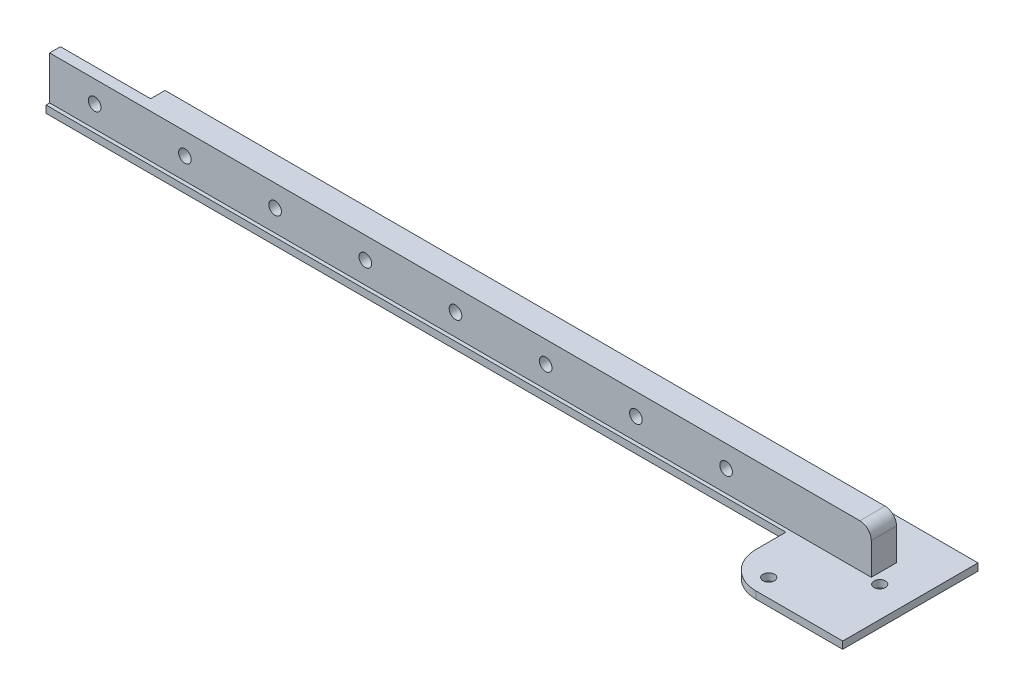
SolidWorks part; units mm, degrees
ref_plane "Front Plane" through (0, 0, 0) normal (0, 0, 1) x (1, 0, 0)
ref_plane "Top Plane" through (0, 0, 0) normal (0, 1, 0) x (1, 0, 0)
ref_plane "Right Plane" through (0, 0, 0) normal (1, 0, 0) x (0, 0, -1)
sketch "TopSketch1" plane through (0, 0, 0) normal (0, 1, 0) x (1, 0, 0)
  line L0 (0, 0) -> (34, 0)
  line L1 (34, 0) -> (34, 37.5)
  line L2 (34, 37.5) -> (0, 37.5)
  line L3 (0, 37.5) -> (0, 26.25)
  line L7 (0, 18.25) -> (0, 0)
  line L8 (0, 18.25) -> (-205.08, 18.25)
  line L9 (-205.08, 18.25) -> (-205.08, 26.25)
  line L10 (-205.08, 26.25) -> (0, 26.25)
  circle A0 centre (8.5, 32.5) radius 1.59
  circle A1 centre (8.5, 5) radius 1.59
  circle A3 centre (25.5, 18.75) radius 1.59
  dimension "D6" = 3.18
  dimension "D1" = 37.5
  dimension "D2" = 34
  dimension "D5" = 8.5
  dimension "D7" = 5
  dimension "D8" = 5
  dimension "D3" = 205.08
  dimension "D4" = 8
  dimension "D9" = 8.5
  dimension "D10" = 18.75
  dimension "D11" = 11.25
  dimension "D12" = 18.25
  dimension "D13" = 239.08
extrude "TopBoss-Extrude1" add sketch "TopSketch1" along normal blind 2
fillet "Fillet1" radius 10 2 edges at (0, 1, 0) (0, 1, -37.5)
sketch "LinearRailHEightSketch2" plane through (0, 2, 0) normal (0, 1, 0) x (1, 0, 0)
  line L0 (0, 26.25) -> (-205.08, 26.25) construction
  line L1 (-205.08, 26.25) -> (22.6667, 26.25)
  line L2 (-205.08, 26.25) -> (-205.08, 19.25)
  line L3 (-205.08, 19.25) -> (22.6667, 19.25)
  line L4 (22.6667, 26.25) -> (22.6667, 19.25)
  line L5 (-205.08, 26.25) -> (-205.08, 18.25) construction
  line L7 (-205.08, 18.25) -> (0, 18.25) construction
  line L8 (34, 0) -> (34, 37.5) construction
  dimension "D1" = 1
  dimension "D2" = 11.3333
extrude "LinearRailHeightBoss-Extrude2" add sketch "LinearRailHEightSketch2" along normal blind 12
sketch "LinearRailHolesSketch3" plane through (0, 0, -19.25) normal (0, 0, 1) x (1, 0, 0)
  line L0 (-205.08, 2) -> (22.6667, 2) construction
  line L1 (-205.08, 14) -> (-205.08, 2) construction
  circle A0 centre (-192.58, 8) radius 1.75
  circle A1 centre (-167.58, 8) radius 1.75
  circle A2 centre (-142.58, 8) radius 1.75
  circle A3 centre (-117.58, 8) radius 1.75
  circle A4 centre (-92.58, 8) radius 1.75
  circle A5 centre (-67.58, 8) radius 1.75
  circle A6 centre (-42.58, 8) radius 1.75
  circle A7 centre (-17.58, 8) radius 1.75
  dimension "D4" = 8
  dimension "D1" = 3.5
  dimension "D2" = 6
  dimension "D3" = 12.5
extrude "LinearRailHolesCut-Extrude1" cut sketch "LinearRailHolesSketch3" against normal through all
sketch "ConnectingPlateSketch2" plane through (0, 0, -26.25) normal (0, 0, -1) x (-1, 0, 0)
  line L0 (-22.6667, 14) -> (205.08, 14) construction
  line L1 (180.08, 14) -> (205.08, 14)
  line L2 (180.08, 14) -> (180.08, 0)
  line L3 (180.08, 0) -> (205.08, 0)
  line L4 (205.08, 14) -> (205.08, 0)
  dimension "D1" = 25
extrude "ConnectingPlateCut-Extrude1" cut sketch "ConnectingPlateSketch2" against normal blind 4
fillet "Fillet2" radius 3.175 1 edges at (22.6667, 14, -22.75)
sketch "NutHoleSketch1" plane through (0, 0, -26.25) normal (0, 0, -1) x (-1, 0, 0)
  line L1 (19.13, 5.3153) -> (20.68, 8)
  line L2 (20.68, 8) -> (19.13, 10.6847)
  line L3 (19.13, 10.6847) -> (16.03, 10.6847)
  line L4 (16.03, 10.6847) -> (14.48, 8)
  line L5 (14.48, 8) -> (16.03, 5.3153)
  line L6 (16.03, 5.3153) -> (19.13, 5.3153)
  line L7 (44.13, 5.3153) -> (45.68, 8)
  line L8 (45.68, 8) -> (44.13, 10.6847)
  line L9 (44.13, 10.6847) -> (41.03, 10.6847)
  line L10 (41.03, 10.6847) -> (39.48, 8)
  line L11 (39.48, 8) -> (41.03, 5.3153)
  line L12 (41.03, 5.3153) -> (44.13, 5.3153)
  line L13 (69.13, 5.3153) -> (70.68, 8)
  line L14 (70.68, 8) -> (69.13, 10.6847)
  line L15 (69.13, 10.6847) -> (66.03, 10.6847)
  line L16 (66.03, 10.6847) -> (64.48, 8)
  line L17 (64.48, 8) -> (66.03, 5.3153)
  line L18 (66.03, 5.3153) -> (69.13, 5.3153)
  line L19 (94.13, 5.3153) -> (95.68, 8)
  line L20 (95.68, 8) -> (94.13, 10.6847)
  line L21 (94.13, 10.6847) -> (91.03, 10.6847)
  line L22 (91.03, 10.6847) -> (89.48, 8)
  line L23 (89.48, 8) -> (91.03, 5.3153)
  line L24 (91.03, 5.3153) -> (94.13, 5.3153)
  line L25 (119.13, 5.3153) -> (120.68, 8)
  line L26 (120.68, 8) -> (119.13, 10.6847)
  line L27 (119.13, 10.6847) -> (116.03, 10.6847)
  line L28 (116.03, 10.6847) -> (114.48, 8)
  line L29 (114.48, 8) -> (116.03, 5.3153)
  line L30 (116.03, 5.3153) -> (119.13, 5.3153)
  line L31 (144.13, 5.3153) -> (145.68, 8)
  line L32 (145.68, 8) -> (144.13, 10.6847)
  line L33 (144.13, 10.6847) -> (141.03, 10.6847)
  line L34 (141.03, 10.6847) -> (139.48, 8)
  line L35 (139.48, 8) -> (141.03, 5.3153)
  line L36 (141.03, 5.3153) -> (144.13, 5.3153)
  line L37 (169.13, 5.3153) -> (170.68, 8)
  line L38 (170.68, 8) -> (169.13, 10.6847)
  line L39 (169.13, 10.6847) -> (166.03, 10.6847)
  line L40 (166.03, 10.6847) -> (164.48, 8)
  line L41 (164.48, 8) -> (166.03, 5.3153)
  line L42 (166.03, 5.3153) -> (169.13, 5.3153)
  circle A0 centre (17.58, 8) radius 2.6847 construction
  circle A1 centre (42.58, 8) radius 2.6847 construction
  circle A2 centre (67.58, 8) radius 2.6847 construction
  circle A3 centre (92.58, 8) radius 2.6847 construction
  circle A4 centre (117.58, 8) radius 2.6847 construction
  circle A5 centre (142.58, 8) radius 2.6847 construction
  circle A6 centre (167.58, 8) radius 2.6847 construction
  dimension "D1" = 6.2
extrude "NutHoleCut-Extrude1" cut sketch "NutHoleSketch1" against normal blind 2
equation "\"GABDepth\"= \"GABDistanceFromBackToFirstPulley\" + \"GABPulleyDDistanceBetween\" + \"GABDistanceFromPulleyToFront\""
equation "\"GABWidth\"= \"StandardWallThickness\" + \"GABDistanceFromLSideToPulley\" + \"GABPulleyWDistanceBetween\" + \"GABDistanceFromPulleyToRSide\""
equation "\"StandardWallThickness\"= 3mm"
equation "\"LinearRailWidth\"= 12mm'Spec"
equation "\"LinearRailHeight\"= 8mm'Spec"
equation "\"GABLRClampHoleOffsetFromSide\"= 5mm"
equation "\"GABDistanceFromBackToFirstPulley\"= 13.5mm"
equation "\"GABPulleyDDistanceBetween\"= 12.5mm'From the100"
equation "\"GABPulleyWDistanceBetween\"= 14.5mm'From the100"
equation "\"GABDistanceFromPulleyToFront\"= 8mm"
equation "\"GABDistanceFromLSideToPulley\"= 9.5mm + \"StandardWallThickness\""
equation "\"GABDistanceFromPulleyToRSide\"= 7.5mm"
equation "\"GABClampBaseHeight\"= 2mm"
equation "\"LinearRailHoleDiameter\"= 3.5mm'Spec"
equation "\"GABDistanceToFrontRearClampHoles\"= 8.5mm"
equation "\"D1@TopSketch1\" = \"GABWidth\""
equation "\"D2@TopSketch1\"=\"GABDepth\""
equation "\"D5@TopSketch1\" = \"GABDistanceToFrontRearClampHoles\""
equation "\"D7@TopSketch1\" = \"GABLRClampHoleOffsetFromSide\""
equation "\"D8@TopSketch1\" = \"GABLRClampHoleOffsetFromSide\""
equation "\"D1@TopBoss-Extrude1\" = \"GABClampBaseHeight\""
equation "\"RailThickness\"= .125in'Spec"
equation "\"D4@TopSketch1\"=\"LinearRailHeight\""
equation "\"D1@LinearRailHeightBoss-Extrude2\" = \"LinearRailWidth\""
equation "\"D1@LinearRailHolesSketch3\" = \"LinearRailHoleDiameter\""
equation "\"D2@LinearRailHolesSketch3\" = \"LinearRailWidth\" / 2"
equation "\"D9@TopSketch1\"=\"GABDistanceToFrontRearClampHoles\""
equation "\"D2@LinearRailHEightSketch2\"=\"GABDepth\"/3"
equation "\"D11@TopSketch1\"=(\"GABWidth\")/2 - \"LinearRailHeight\"+1/2"
equation "\"LinearRailHoleDistance\"= 25mm'Spec"
equation "\"D1@ConnectingPlateSketch2\" = \"LinearRailHoleDistance\""
equation "\"D1@ConnectingPlateCut-Extrude1\"=\"LinearRailHeight\"/2"
equation "\"D1@Fillet2\"=\"RailThickness\""
equation "\"LinearRailSupportNutWidth\"= 6.2mm"
equation "\"D1@NutHoleSketch1\"=\"LinearRailSupportNutWidth\""
equation "\"LinearRailSupportNutHoleDepth\" = \"LinearRailHeight\" / 4"
equation "\"D1@NutHoleCut-Extrude1\"=\"LinearRailSupportNutHoleDepth\""
